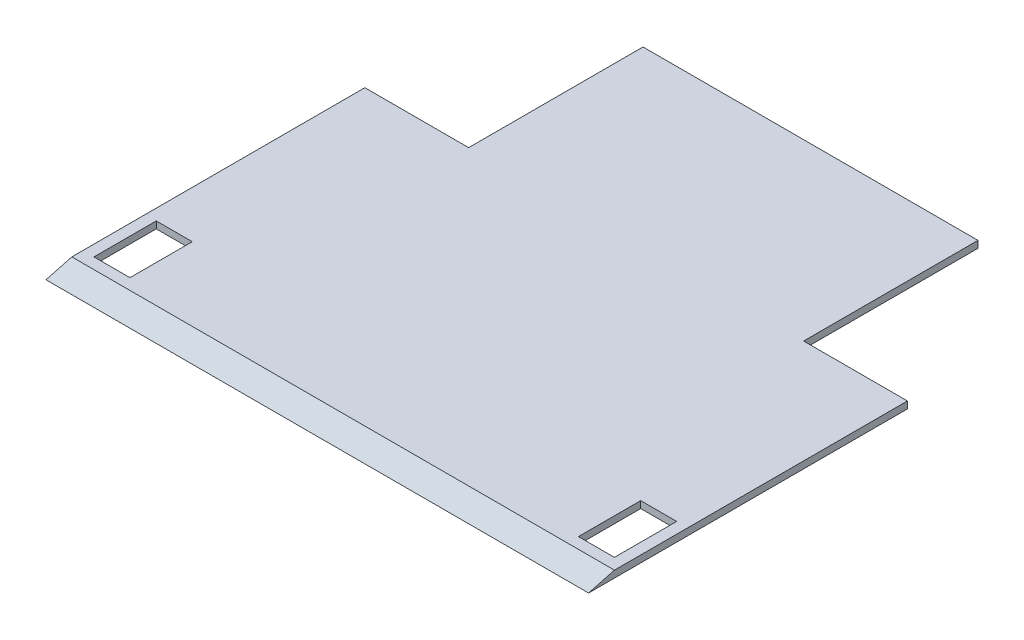
SolidWorks part; units mm, degrees
ref_plane "Alzado" through (0, 0, 0) normal (0, 0, 1) x (1, 0, 0)
ref_plane "Planta" through (0, 0, 0) normal (0, 1, 0) x (1, 0, 0)
ref_plane "Vista lateral" through (0, 0, 0) normal (1, 0, 0) x (0, 0, -1)
sketch "Croquis1" plane through (0, 0, 0) normal (1, 0, 0) x (0, 0, -1)
  line L0 (0, 0) -> (178.17, 0)
  line L1 (178.17, 0) -> (178.17, 2.5)
  line L2 (178.17, 2.5) -> (9.3301, 2.5)
  line L3 (0, 0) -> (9.3301, 2.5)
  dimension "D1" = 178.17
  dimension "D2" = 2.5
  dimension "D3" = 165
extrude "Saliente-Extruir1" add sketch "Croquis1" along normal blind 196
sketch "Croquis2" plane through (0, 0, 0) normal (0, -1, 0) x (-1, 0, 0)
  line L1 (-37.5, 115.1801) -> (0, 115.1801)
  line L2 (-37.5, 115.1801) -> (-37.5, 178.17)
  line L3 (-37.5, 178.17) -> (0, 178.17)
  line L4 (0, 115.1801) -> (0, 178.17)
  line L5 (-37.5, 115.1801) -> (0, 178.17) construction
  line L6 (-37.5, 178.17) -> (0, 115.1801) construction
  line L7 (-158.5, 115.1801) -> (-196, 115.1801)
  line L8 (-158.5, 115.1801) -> (-158.5, 178.17)
  line L9 (-158.5, 178.17) -> (-196, 178.17)
  line L10 (-196, 115.1801) -> (-196, 178.17)
  line L11 (-158.5, 115.1801) -> (-196, 178.17) construction
  line L12 (-158.5, 178.17) -> (-196, 115.1801) construction
  point P4 (-18.75, 146.6751)
  point P11 (-177.25, 146.6751)
extrude "Cortar-Extruir1" cut sketch "Croquis2" against normal up to next
sketch "Croquis4" plane through (0, 2.5, 0) normal (0, 1, 0) x (1, 0, 0)
  line L7 (4, 13.3301) -> (17, 13.3301)
  line L8 (4, 13.3301) -> (4, 35.8301)
  line L9 (4, 35.8301) -> (17, 35.8301)
  line L10 (17, 13.3301) -> (17, 35.8301)
  line L11 (4, 13.3301) -> (17, 35.8301) construction
  line L12 (4, 35.8301) -> (17, 13.3301) construction
  point P9 (10.5, 24.5801)
  dimension "D3" = 22.5
  dimension "D4" = 13
extrude "Cortar-Extruir2" cut sketch "Croquis4" against normal up to next
ref_plane "Plano1" through (98, 0, 0) normal (1, 0, 0) x (0, 0, -1)
mirror "Simetría1" about plane through (98, 0, 0) normal (1, 0, 0) of "Cortar-Extruir2"
